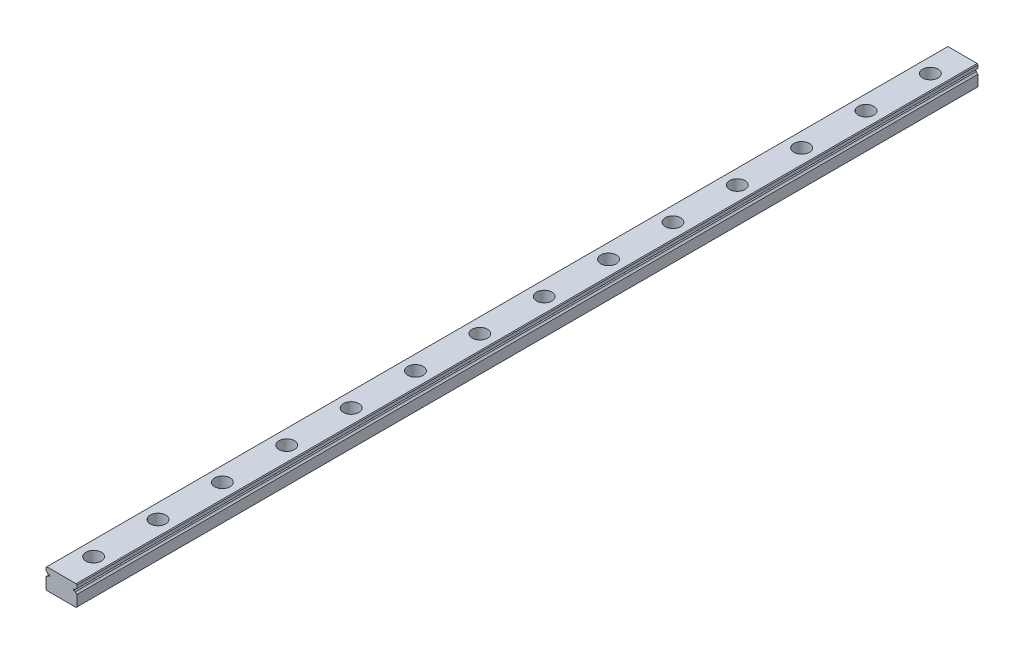
SolidWorks part; units mm, degrees
ref_plane "Спереди" through (0, 0, 0) normal (0, 0, 1) x (1, 0, 0)
ref_plane "Сверху" through (0, 0, 0) normal (0, 1, 0) x (1, 0, 0)
ref_plane "Справа" through (0, 0, 0) normal (1, 0, 0) x (0, 0, -1)
sketch "Эскиз1" plane through (0, 0, 0) normal (0, 0, 1) x (1, 0, 0)
  line L0 (-6, 3.7) -> (-5.7, 4)
  line L1 (-5.7, -4) -> (5.7, -4)
  line L2 (-6, -3.7) -> (-6, 0.549)
  line L3 (-5.7, 4) -> (5.7, 4)
  line L4 (6, -3.7) -> (6, 0.549)
  line L5 (-6, -4) -> (6, 4) construction
  line L6 (-6, 4) -> (6, -4) construction
  line L7 (-6, -3.7) -> (-5.7, -4)
  line L8 (5.7, -4) -> (6, -3.7)
  line L9 (5.7, 4) -> (6, 3.7)
  line L10 (-6, 2.451) -> (-6, 3.7)
  line L11 (-5.3546, 1.7981) -> (-4.6435, 1.7981)
  line L12 (0, 5.4188) -> (0, -5.747) construction
  line L13 (-5.3546, 1.2019) -> (-4.6435, 1.2019)
  line L14 (-4.6435, 1.7981) -> (-4.6435, 1.2019)
  line L15 (4.6435, 1.7981) -> (4.6435, 1.2019)
  line L16 (5.3546, 1.2019) -> (4.6435, 1.2019)
  line L17 (5.3546, 1.7981) -> (4.6435, 1.7981)
  line L18 (6, 2.451) -> (6, 3.7)
  line L19 (4.6435, 1.7981) -> (5.3546, 1.7981) construction
  arc A0 (-6, 0.549) -> (-5.3546, 1.2019) centre (-6.3091, 1.5) ccw
  arc A1 (-5.3546, 1.7981) -> (-6, 2.451) centre (-6.3091, 1.5) ccw
  arc A2 (5.3546, 1.7981) -> (6, 2.451) centre (6.3091, 1.5) cw
  arc A3 (6, 0.549) -> (5.3546, 1.2019) centre (6.3091, 1.5) cw
  point P0 (0, 0)
extrude "Extrusion1" add sketch "Эскиз1" along normal blind 350
sketch "Эскиз2" plane through (0, 4, 0) normal (0, 1, 0) x (1, 0, 0)
  line L0 (0, 0) -> (0, -26.2396) construction
  line L1 (5.7, 0) -> (-5.7, 0) construction
  line L2 (-3.8306, -12.5) -> (3.8306, -12.5) construction
  circle A0 centre (0, -12.5) radius 3
  circle A1 centre (0, -12.5) radius 1.75
  dimension "D2" = 3.5
  dimension "D3" = 6
  dimension "D1" = 12.5
extrude "Вырез-Вытянуть1" cut sketch "Эскиз2" against normal blind 4.5
extrude "Вырез-Вытянуть2" cut sketch "Эскиз2<2>" against normal through all contours A1 region at (0, 4, 12.5)
sketch "Эскиз2<2>" plane through (0, 4, 0) normal (0, 1, 0) x (1, 0, 0) same geometry as "Эскиз2"
pattern_linear "Линейный массив1" count 14 spacing 25 along (0, 0, 1) of "Вырез-Вытянуть1", "Вырез-Вытянуть2"
